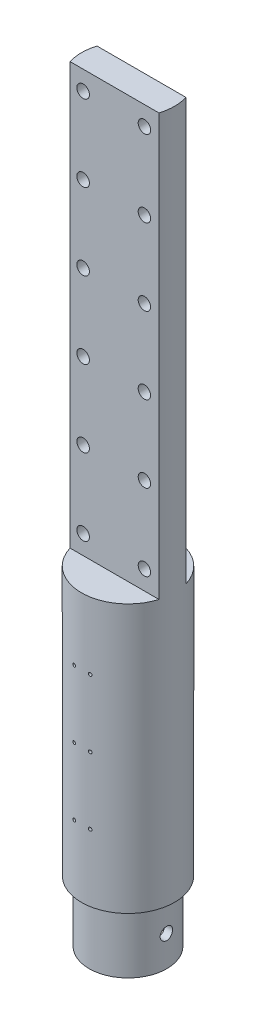
SolidWorks part; units mm, degrees
ref_plane "Front Plane" through (0, 0, 0) normal (0, 0, 1) x (1, 0, 0)
ref_plane "Top Plane" through (0, 0, 0) normal (0, 1, 0) x (1, 0, 0)
ref_plane "Right Plane" through (0, 0, 0) normal (1, 0, 0) x (0, 0, -1)
sketch "Sketch1" plane through (0, 0, 0) normal (0, 1, 0) x (1, 0, 0)
  circle A0 centre (0, 0) radius 25.35
  circle A1 centre (0, 0) radius 30.35
  circle A2 centre (0, 0) radius 20.35
  dimension "D1" = 50.7
  dimension "D2" = 60.7
  dimension "D3" = 5
extrude "Boss-Extrude2" add sketch "Sketch1" along normal blind 450 contours A1 A0 | A0 A2 | A2 region at (-24.633, 0, 0) region at (-29.4916, 0, 0) region at (0, 0, 0)
extrude "Boss-Extrude3" add sketch "Sketch1<3>" against normal blind 40 contours A0 A2 region at (-24.633, 0, 0)
sketch "Sketch1<3>" plane through (0, 0, 0) normal (0, 1, 0) x (1, 0, 0) same geometry as "Sketch1"
sketch "Sketch6" plane through (0, 450, 0) normal (0, 1, 0) x (1, 0, 0)
  line L0 (0, 0) -> (0, -30.35)
  line L1 (0, -33.8) -> (25, -33.8)
  line L2 (0, -33.8) -> (-25, -33.8)
  line L3 (-25, -33.8) -> (-25, -13.8)
  line L4 (-25, -13.8) -> (0, -13.8)
  line L5 (25, -33.8) -> (25, -13.8)
  line L6 (25, -13.8) -> (0, -13.8)
  line L7 (0, -13.8) -> (0.1122, -13.8)
  line L8 (0, 13.8) -> (0.1122, 13.8)
  line L9 (25, 13.8) -> (0, 13.8)
  line L10 (25, 33.8) -> (25, 13.8)
  line L11 (-25, 13.8) -> (0, 13.8)
  line L12 (-25, 33.8) -> (-25, 13.8)
  line L13 (0, 33.8) -> (-25, 33.8)
  line L14 (0, 33.8) -> (25, 33.8)
  line L15 (-45, 0) -> (45, 0)
  line L16 (25, -13.8) -> (42.8318, -13.8)
  line L17 (42.8318, -13.8) -> (-42.8318, -13.8)
  line L18 (25, 13.8) -> (42.8318, 13.8)
  line L19 (-25, 13.8) -> (-42.8318, 13.8)
  line L20 (29.0462, -8.8) -> (-29.0462, -8.8)
  line L21 (29.0462, 8.8) -> (-29.0462, 8.8)
  circle A0 centre (0, 0) radius 30.35
  circle A1 centre (0, -32.075) radius 1.725
  circle A2 centre (0, 32.075) radius 1.725
  circle A4 centre (0, 0) radius 45
  circle M28 centre (0, 0) radius 30.35
  dimension "D1" = 60.7
  dimension "D2" = 3.45
  dimension "D3" = 25
  dimension "D4" = 25
  dimension "D5" = 20
  dimension "D6" = 5
  dimension "D7" = 5
extrude "Cut-Extrude3" cut sketch "Sketch6" against normal blind 275 contours A0 L5 L1 L2 L3 L17 | A1 L1 L5 A0 | L0 A0 L5 L6 | L3 A0 L0 L4 | A1 A0 L3 L2 | L10 A0 L12 L11 L8 L9 | A0 L18 L19 L12 L13 L14 L10 | L14 A2 A0 L10 | A0 A2 L13 L12 | L12 A0 L19 | L18 A0 L10 | L5 A0 L16 | L17 A0 L3 | L20 L0 L6 L16 M28 | L0 L20 L17 L4 M28 | L21 L18 L9 L8 L11 L19 M28 | A1 | A2 region at (10.4704, 450, 20.669) region at (-14.0685, 450, 11.2702) region at (-10.4704, 450, 20.669) region at (14.0685, 450, 11.2702) region at (-16.38, 450, 29.097) region at (16.38, 450, 29.097) region at (-25.6941, 450, 14.9635) region at (-25.9117, 450, 25.5041) region at (25.6941, 450, 14.9635) region at (0, 450, -11.2702) region at (34.9315, 450, -14.7117) region at (25.6941, 450, -14.9635) region at (-25.6941, 450, -14.9635) region at (0, 450, -20.669) region at (16.38, 450, -29.097) region at (-16.38, 450, -29.097)
ref_plane "Plane1" through (0, 0, 30.35) normal (0, 0, 1) x (1, 0, 0)
sketch "Sketch8" plane through (0, 0, 30.35) normal (0, 0, 1) x (1, 0, 0)
  line L0 (0, 175) -> (0, 0)
  line L1 (29.0462, 175) -> (-29.0462, 175) construction
  line L3 (-30.35, 450) -> (-30.35, 0) construction
  line L5 (30.35, 0) -> (30.35, 450) construction
  line L6 (0, 87.5) -> (0, 175)
  line L7 (0, 131.25) -> (5.215, 131.25)
  line L8 (0, 131.25) -> (-5.215, 131.25)
  line L9 (0, 87.5) -> (0, 0)
  line L10 (0, 43.75) -> (30.35, 43.75)
  line L11 (-30.35, 43.75) -> (0, 43.75)
  circle A0 centre (5.215, 131.25) radius 1.05
  circle A1 centre (-5.215, 131.25) radius 1.05
  circle A2 centre (-5.215, 87.5) radius 1.05
  circle A3 centre (5.215, 87.5) radius 1.05
  circle A4 centre (-5.215, 43.75) radius 1.05
  circle A5 centre (5.215, 43.75) radius 1.05
  dimension "D5" = 2.1
  dimension "D6" = 2.1
  dimension "D3" = 5.215
  dimension "D4" = 5.215
  dimension "D7" = 3
extrude "Cut-Extrude5" cut sketch "Sketch8" against normal blind 137 contours A2 | A3 | A1 | A0 | A4 | A5
sketch "Sketch9" plane through (0, 0, 0) normal (1, 0, 0) x (0, 0, -1)
  line L0 (25.35, -20) -> (-25.35, -20)
  line L1 (25.35, -40) -> (25.35, 0) construction
  line L2 (-25.35, 0) -> (-25.35, -40) construction
  circle A0 centre (0, -20) radius 4.05
  dimension "D1" = 8.1
extrude "Cut-Extrude6" cut sketch "Sketch9" against normal blind 137 and the other way blind 137 contours A0
sketch "Sketch10" plane through (0, 0, -8.8) normal (0, 0, -1) x (-1, 0, 0)
  line L0 (0.4942, 237.5352) -> (0.4942, 175)
  line L1 (-19.5058, 237.5352) -> (20.4942, 237.5352)
  line L3 (-29.0462, 175) -> (29.0462, 175) construction
  circle A0 centre (-19.5058, 237.5352) radius 4.05
  circle A1 centre (20.4942, 237.5352) radius 4.1
  circle A2 centre (-19.5058, 287.5352) radius 4.05
  circle A3 centre (20.4942, 287.5352) radius 4.1
  circle A4 centre (-19.5058, 337.5352) radius 4.05
  circle A5 centre (20.4942, 337.5352) radius 4.1
  circle A6 centre (-19.5058, 387.5352) radius 4.05
  circle A7 centre (20.4942, 387.5352) radius 4.1
  circle A8 centre (-19.5058, 187.5352) radius 4.05
  circle A9 centre (20.4942, 187.5352) radius 4.1
  circle A10 centre (-19.5058, 437.5352) radius 4.05
  circle A11 centre (20.4942, 437.5352) radius 4.1
  dimension "D2" = 8.1
  dimension "D3" = 8.2
  dimension "D1" = 40
  dimension "D4" = 2
extrude "Cut-Extrude7" cut sketch "Sketch10" against normal blind 137 contours A2 | A0 | A1 | A8 | A9 | A3 | A5 | A4 | A7 | A6 | A10 | A11
